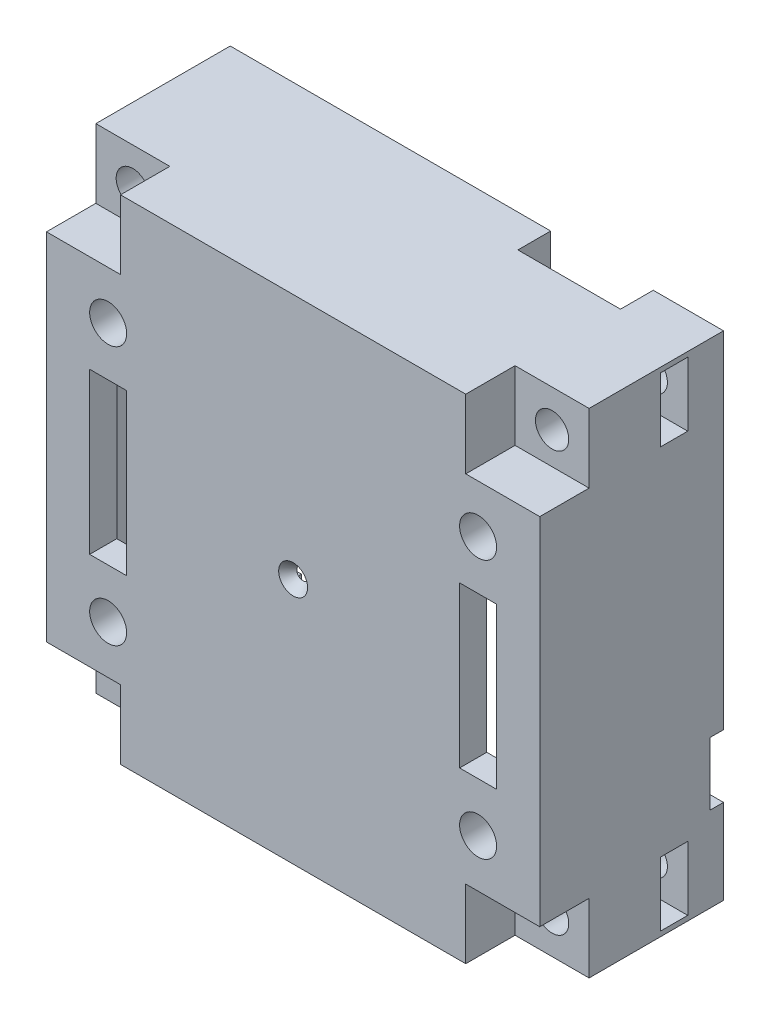
SolidWorks part; units mm, degrees
ref_plane "前视基准面" through (0, 0, 0) normal (0, 0, 1) x (1, 0, 0)
ref_plane "上视基准面" through (0, 0, 0) normal (0, 1, 0) x (1, 0, 0)
ref_plane "右视基准面" through (0, 0, 0) normal (1, 0, 0) x (0, 0, -1)
ref_plane "基准面1" through (0, 0, -12.4) normal (0, 0, -1) x (-1, 0, 0)
sketch "草图1" plane through (0, 0, -12.4) normal (0, 0, -1) x (-1, 0, 0)
  line L0 (1.7705, -8.8673) -> (1.7705, 31.1327)
  line L1 (1.7705, 31.1327) -> (-38.2295, 31.1327)
  line L2 (-38.2295, 31.1327) -> (-38.2295, -8.8673)
  line L3 (-38.2295, -8.8673) -> (1.7705, -8.8673)
  point P6 (-18.2295, 11.1327)
extrude "凸台-拉伸1" add sketch "草图1" against normal blind 12.7
ref_plane "基准面2" through (0, 0, -8) normal (0, 0, 1) x (1, 0, 0)
sketch "草图2" plane through (0, 0, -8) normal (0, 0, 1) x (1, 0, 0)
  line L0 (-2.0183, -8.4692) -> (2.7317, -8.4692)
  line L1 (2.7317, -8.4692) -> (4.2317, -5.8712)
  line L2 (4.2317, -5.8712) -> (2.7295, -3.2692)
  line L3 (2.7295, -3.2692) -> (-2.0183, -3.2692)
  line L4 (-2.0183, -3.2692) -> (-2.0183, -8.4692)
  line L5 (-1.7705, -8.8673) -> (-1.7705, 31.1327) construction
  line L6 (38.2295, -8.8673) -> (-1.7705, -8.8673) construction
  line L7 (2.7317, -8.4692) -> (-2.4592, 0.5217) construction
  line L9 (18.2295, 53.4111) -> (18.2295, -31.5909) construction
  line L10 (63.1299, 11.1327) -> (-18.8321, 11.1327) construction
  line L11 (-2.0183, 25.5346) -> (-2.0183, 30.7346)
  line L12 (2.7295, 25.5346) -> (-2.0183, 25.5346)
  line L13 (38.4773, 30.7346) -> (33.7273, 30.7346)
  line L14 (33.7273, 30.7346) -> (32.2273, 28.1365)
  line L15 (32.2273, 28.1365) -> (33.7295, 25.5346)
  line L16 (33.7295, 25.5346) -> (38.4773, 25.5346)
  line L21 (4.2317, 28.1365) -> (2.7295, 25.5346)
  line L22 (2.7317, 30.7346) -> (4.2317, 28.1365)
  line L23 (-2.0183, 30.7346) -> (2.7317, 30.7346)
  line L24 (38.4773, 25.5346) -> (38.4773, 30.7346)
  line L25 (38.4773, -3.2692) -> (38.4773, -8.4692)
  line L26 (33.7295, -3.2692) -> (38.4773, -3.2692)
  line L27 (32.2273, -5.8712) -> (33.7295, -3.2692)
  line L28 (33.7273, -8.4692) -> (32.2273, -5.8712)
  line L29 (38.4773, -8.4692) -> (33.7273, -8.4692)
  line L30 (-2.5019, -12.3303) -> (2.7295, -3.2692) construction
  point P26 (1.2295, -5.8673)
  point P34 (1.2295, -5.8673)
  dimension "D2" = 3
  dimension "D3" = 3
  dimension "D4" = 60
  dimension "D5" = 60
  dimension "D6" = 4.75
  dimension "D8" = 120
  dimension "D9" = 120
  dimension "D11" = 5.2
  dimension "D13" = 3
extrude "切除-拉伸2" cut sketch "草图2" against normal blind 1.5 and the other way blind 0.7
ref_plane "基准面3" through (0, 0, -5) normal (0, 0, -1) x (-1, 0, 0)
sketch "草图8" plane through (0, 0, -12.4) normal (0, 0, -1) x (-1, 0, 0)
  line L0 (-0.0295, 25.3327) -> (-36.4295, 25.3327)
  line L1 (-36.4295, 25.3327) -> (-36.4295, -3.0673)
  line L2 (-36.4295, -3.0673) -> (-0.0295, -3.0673)
  line L3 (-0.0295, -3.0673) -> (-0.0295, 25.3327)
extrude "切除-拉伸4" cut sketch "草图8" against normal up to surface (12.7 mm away) up to face at (18.2295, 11.1327, 0.3)
sketch "草图10" plane through (0, 0, 0.3) normal (0, 0, 1) x (1, 0, 0)
  line L1 (0.0295, 25.3327) -> (0.0295, -3.0673) construction
  line L2 (0.0295, -3.0673) -> (36.4295, -3.0673) construction
  line L3 (-1.7705, 25.5346) -> (4.2317, 25.5346)
  line L9 (36.4295, 25.3327) -> (0.0295, -3.0673) construction
  line L10 (36.4295, -3.0673) -> (0.0295, 25.3327) construction
  line L15 (36.4295, 25.3327) -> (0.0295, -3.0673) construction
  line L16 (36.4295, -3.0673) -> (0.0295, 25.3327) construction
  line L17 (4.2317, 25.5346) -> (4.2317, 31.1327)
  line L18 (-1.7705, 31.1327) -> (38.2295, 31.1327) construction
  line L19 (4.2317, 31.1327) -> (32.2273, 31.1327)
  line L20 (-1.7705, 25.5346) -> (-1.7705, -3.2692)
  line L21 (38.2295, 31.1327) -> (38.2295, -8.8673) construction
  line L31 (32.2273, 25.5346) -> (32.2273, 31.1327)
  line L48 (40.0436, 11.1327) -> (-13.5796, 11.1327) construction
  line L53 (22.8295, 16.6327) -> (13.6295, 5.6327) construction
  line L54 (22.8295, 5.6327) -> (13.6295, 16.6327) construction
  line L55 (1.7295, 17.6327) -> (4.7295, 17.6327)
  line L56 (18.2295, 36.1745) -> (18.2295, -22.808) construction
  line L57 (1.7295, 4.6327) -> (1.7295, 17.6327)
  line L58 (4.7295, 4.6327) -> (1.7295, 4.6327)
  line L59 (4.7295, 17.6327) -> (4.7295, 4.6327)
  line L60 (31.7295, 17.6327) -> (31.7295, 4.6327)
  line L61 (31.7295, 4.6327) -> (34.7295, 4.6327)
  line L62 (34.7295, 4.6327) -> (34.7295, 17.6327)
  line L63 (34.7295, 17.6327) -> (31.7295, 17.6327)
  line L64 (3.2295, 0.6327) -> (3.2295, 21.6327) construction
  line L65 (38.2295, 25.5346) -> (32.2273, 25.5346)
  line L66 (38.2295, 25.5346) -> (38.2295, -3.2692)
  line L67 (-1.7705, -3.2692) -> (4.2317, -3.2692)
  line L68 (4.2317, -3.2692) -> (4.2317, -8.8673)
  line L69 (4.2317, -8.8673) -> (32.2273, -8.8673)
  line L70 (32.2273, -3.2692) -> (32.2273, -8.8673)
  line L71 (38.2295, -3.2692) -> (32.2273, -3.2692)
  line L72 (17.7295, 10.6327) -> (18.7295, 11.6327) construction
  line L73 (17.7295, 11.6327) -> (18.7295, 10.6327) construction
  circle A0 centre (18.2295, 11.1327) radius 0.5
  circle A16 centre (3.2295, 0.6327) radius 1.5
  circle A17 centre (3.2295, 21.6327) radius 1.5
  circle A18 centre (33.2295, 21.6327) radius 1.5
  circle A19 centre (33.2295, 0.6327) radius 1.5
  point P11 (18.2295, 11.1327)
  point P12 (18.2295, 11.1327)
  point P13 (18.2295, 11.1327)
  point P25 (18.2295, 31.1327)
  point P26 (18.2295, 11.1327)
  point P33 (-1.7705, 11.1327)
  point P42 (38.2295, 11.1327)
  dimension "D5" = 13
  dimension "D6" = 3
  dimension "D7" = 3
  dimension "D11" = 1
  dimension "D1" = 21
  dimension "D2" = 30
  dimension "D3" = 11
  dimension "D4" = 9.2
  dimension "D8" = 3
  dimension "D9" = 1
  dimension "D10" = 1
extrude "凸台-拉伸2" add sketch "草图10" along normal blind 2.2 separate body
sketch "草图13" plane through (0, 0, -12.4) normal (0, 0, -1) x (-1, 0, 0)
  line L0 (10.4025, 11.1327) -> (-53.3827, 11.1327) construction
  line L3 (-18.2295, -16.9604) -> (-18.2295, 39.7747) construction
  circle A0 centre (-35.2295, -5.8673) radius 1.35
  circle A1 centre (-1.2295, -5.8673) radius 1.35
  circle A2 centre (-1.2295, 28.1327) radius 1.35
  circle A3 centre (-35.2295, 28.1327) radius 1.35
  dimension "D2" = 2.7
extrude "切除-拉伸6" cut sketch "草图13" against normal up to surface (12.7 mm away) up to face at (18.2295, 11.1327, 0.3)
fillet "圆角1" radius 1 4 edges at (36.4295, 25.3327, -6.05) (36.4295, -3.0673, -6.05) (0.0295, -3.0673, -6.05) (0.0295, 25.3327, -6.05)
sketch "草图14" plane through (0, -8.8673, 0) normal (0, -1, 0) x (1, 0, 0)
  line L0 (38.2295, -12.4) -> (-1.7705, -12.4) construction
  line L8 (4.0099, -12.4) -> (12.3299, -12.4)
  line L9 (12.3299, -12.4) -> (12.3299, -9.75)
  line L10 (12.3299, -9.75) -> (4.0099, -9.75)
  line L11 (4.0099, -9.75) -> (4.0099, -12.4)
extrude "切除-拉伸8" cut sketch "草图14" against normal up to next (5.8 mm away)
sketch "草图15" plane through (0, -8.8673, 0) normal (0, -1, 0) x (1, 0, 0)
  line L0 (17.3459, -12.4) -> (30.2459, -12.4)
  line L1 (38.2295, -12.4) -> (12.3299, -12.4) construction
  line L3 (30.2459, -5.1) -> (17.3459, -5.1)
  line L4 (30.2459, -5.1) -> (30.2459, -12.4)
  line L28 (17.3459, -5.1) -> (17.3459, -12.4)
  dimension "D1" = 7.3
extrude "切除-拉伸9" cut sketch "草图15" against normal up to next (5.8 mm away)
sketch "草图16" plane through (38.2295, 0, 0) normal (1, 0, 0) x (0, 0, -1)
  line L0 (12.4, -1.9836) -> (11.3145, -1.9836)
  line L1 (12.4, 31.1327) -> (12.4, -8.8673) construction
  line L2 (11.3145, -1.9836) -> (11.3145, 3.1167)
  line L3 (11.3145, 3.1167) -> (12.4, 3.1167)
  line L4 (12.4, 3.1167) -> (12.4, -1.9836)
extrude "切除-拉伸10" cut sketch "草图16" against normal up to next (1.8 mm away)
sketch "草图17" plane through (0, 31.1327, 0) normal (0, 1, 0) x (1, 0, 0)
  line L0 (32.533, 12.4) -> (32.533, 9.7407)
  line L1 (-1.7705, 12.4) -> (38.2295, 12.4) construction
  line L2 (24.213, 12.4) -> (32.533, 12.4)
  line L3 (24.213, 12.4) -> (24.213, 9.7407)
  line L10 (24.213, 9.7407) -> (32.533, 9.7407)
extrude "切除-拉伸11" cut sketch "草图17" against normal up to next (5.8 mm away)
ref_axis "基准轴1" through (18.2295, 11.1327, 2.5) along (0, 0, -1)
ref_plane "基准面4" through (0, 11.1327, 0) normal (0, -1, 0) x (-1, 0, 0)
sketch "草图23" plane through (0, 0, 2.5) normal (0, 0, 1) x (1, 0, 0)
  line L0 (32.2273, 25.5346) -> (32.2273, 31.1327)
  line L1 (32.2273, 31.1327) -> (38.2295, 31.1327)
  line L2 (38.2295, 31.1327) -> (38.2295, 25.5346)
  line L3 (38.2295, 25.5346) -> (32.2273, 25.5346)
  line L4 (32.2273, -3.2692) -> (32.2273, -8.8673)
  line L5 (32.2273, -8.8673) -> (32.2273, -3.2692) construction
  line L6 (4.2317, -8.8673) -> (32.2273, -8.8673) construction
  line L7 (32.2273, -8.8673) -> (38.2295, -8.8673)
  line L8 (38.2295, -8.8673) -> (38.2295, -3.2692)
  line L9 (32.2273, -3.2692) -> (38.2295, -3.2692) construction
  line L10 (38.2295, -3.2692) -> (38.2295, 25.5346) construction
  line L11 (38.2295, -3.2692) -> (32.2273, -3.2692)
  line L12 (4.2317, -8.8673) -> (4.2317, -3.2692)
  line L13 (4.2317, -3.2692) -> (-1.7705, -3.2692)
  line L14 (-1.7705, -3.2692) -> (-1.7705, -8.8673)
  line L15 (-1.7705, -8.8673) -> (4.2317, -8.8673)
  line L16 (4.2317, 25.5346) -> (-1.7705, 25.5346)
  line L17 (4.2317, 25.5346) -> (-1.7705, 25.5346) construction
  line L18 (-1.7705, 25.5346) -> (-1.7705, 31.1327)
  line L19 (-1.7705, 31.1327) -> (4.2317, 31.1327)
  line L20 (4.2317, 31.1327) -> (4.2317, 25.5346)
extrude "切除-拉伸12" cut sketch "草图23" against normal blind 4
sketch "草图24" plane through (0, 0, 0.3) normal (0, 0, -1) x (-1, 0, 0)
  line L1 (-12.7295, 18.1327) -> (-23.7295, 18.1327)
  line L2 (-12.7295, 18.1327) -> (-12.7295, 4.1327)
  line L3 (-12.7295, 4.1327) -> (-23.7295, 4.1327)
  line L4 (-23.7295, 18.1327) -> (-23.7295, 4.1327)
  line L5 (-12.7295, 18.1327) -> (-23.7295, 4.1327) construction
  line L6 (-12.7295, 4.1327) -> (-23.7295, 18.1327) construction
  circle A0 centre (-18.2295, 11.1327) radius 0.5 construction
  point P11 (-18.2295, 11.1327)
  dimension "D1" = 14
  dimension "D2" = 11
extrude "切除-拉伸14" cut sketch "草图24" against normal blind 1.4
sketch "草图22" plane through (0, 11.1327, 0) normal (0, -1, 0) x (-1, 0, 0)
  line L0 (-18.7295, -1.7) -> (-19.4008, -2.5)
  line L1 (-19.4008, -2.5) -> (-18.2295, -2.5)
  line L3 (-18.7295, -1.7) -> (-18.2295, -1.7)
  line L5 (-18.2295, -5.0619) -> (-18.2295, 2.0112) construction
  line L6 (-18.2295, -2.5) -> (-18.2295, -1.7)
  line L11 (-17.7295, -1.7) -> (-18.7295, -1.7) construction
  line L12 (-34.7295, -2.5) -> (-31.7295, -2.5) construction
  line L16 (-18.7295, -2.5) -> (-17.7295, -2.5) construction
  dimension "D1" = 50
  dimension "D2" = 0.5
revolve "切除-旋转3" cut sketch "草图22" angle 360 about L5
combine bodies "组合1" operation type add bodies to combine 152 153
